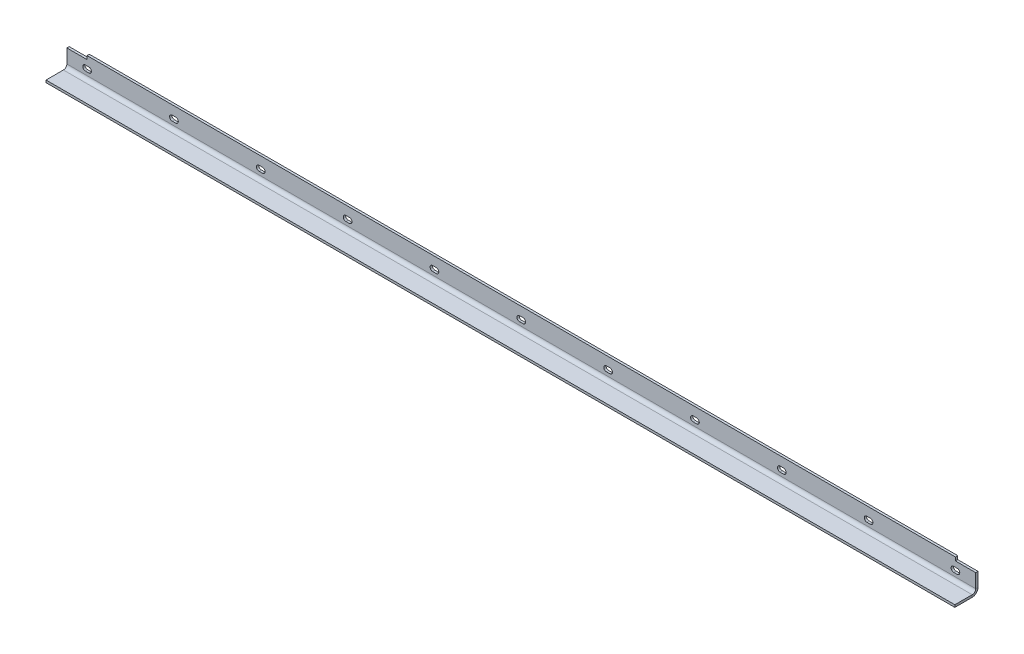
SolidWorks part; units mm, degrees
note: The reader was unsure of these and kept them because the rebuilt part matched: flange length of "Edge-Flange1".
material "ASTM A36 Steel"
ref_plane "Front Plane" through (0, 0, 0) normal (0, 0, 1) x (1, 0, 0)
ref_plane "Top Plane" through (0, 0, 0) normal (0, 1, 0) x (1, 0, 0)
ref_plane "Right Plane" through (0, 0, 0) normal (1, 0, 0) x (0, 0, -1)
sketch "Sketch1" plane through (0, 0, 0) normal (0, 1, 0) x (1, 0, 0)
  line L1 (305.3763, 40) -> (-1264.6237, 40)
  line L2 (305.3763, 40) -> (305.3763, 0)
  line L3 (305.3763, 0) -> (-1264.6237, 0)
  line L4 (-1264.6237, 40) -> (-1264.6237, 0)
  dimension "D1" = 40
  dimension "D2" = 1570
base flange "Base-Flange1" sketch "Sketch1" thickness 4 reverse thickness direction no parameters "D1"=2.5
edge flange "Edge-Flange1" sketch "Sketch8" flange angle 90 flange length 40 flange position material inside bend radius 6 thickness 4 relief rectangular parameters "D6"=10
sketch "Sketch8" plane through (0, 0, -40) normal (0, 0, 1) x (1, 0, 0)
  line L1 (305.3763, 0) -> (-1264.6237, 0) construction
  line L2 (-1264.6237, 0) -> (-1264.6237, 36)
  line L3 (-1264.6237, 36) -> (305.3763, 36)
  line L4 (305.3763, 36) -> (305.3763, 0)
  line L5 (305.3763, 0) -> (-1264.6237, 0)
bend "EdgeBend1" bend radius 6 bend angle 90 parameters "D5"=1
sketch "Sketch9" plane through (0, 0, -36) normal (0, 0, 1) x (1, 0, 0)
  line L0 (305.3763, 36) -> (305.3763, 30)
  line L1 (305.3763, 6) -> (305.3763, 36) construction
  line L2 (305.3763, 30) -> (270.3763, 30)
  line L3 (270.3763, 30) -> (270.3763, 36)
  line L4 (305.3763, 36) -> (-1264.6237, 36) construction
  line L5 (270.3763, 36) -> (305.3763, 36)
  line L6 (-1264.6237, 36) -> (-1264.6237, 30)
  line L7 (-1264.6237, 36) -> (-1264.6237, 6) construction
  line L8 (-1264.6237, 30) -> (-1229.6237, 30)
  line L9 (-1229.6237, 30) -> (-1229.6237, 36)
  line L10 (-1229.6237, 36) -> (-1264.6237, 36)
  dimension "D1" = 35
  dimension "D2" = 6
  dimension "D3" = 35
extrude "Cut-Extrude1" cut sketch "Sketch9" against normal blind 10 normal cut yes
sketch "Sketch10" plane through (0, 0, -36) normal (0, 0, 1) x (1, 0, 0)
  line L0 (273.3763, 16) -> (267.3763, 16) construction
  line L1 (273.3763, 11.5) -> (267.3763, 11.5)
  line L2 (273.3763, 20.5) -> (267.3763, 20.5)
  line L3 (305.3763, 6) -> (305.3763, 30) construction
  line L4 (270.3763, 36) -> (-1229.6237, 36) construction
  arc A0 (273.3763, 11.5) -> (273.3763, 20.5) centre (273.3763, 16) ccw
  arc A1 (267.3763, 20.5) -> (267.3763, 11.5) centre (267.3763, 16) ccw
  point P2 (270.3763, 16)
  dimension "D1" = 32
  dimension "D2" = 9
  dimension "D3" = 20
  dimension "D4" = 6
extrude "Cut-Extrude2" cut sketch "Sketch10" against normal blind 10 normal cut yes
pattern_linear "LPattern1" count 11 spacing 150 along (-1, 0, 0) of "Cut-Extrude2"
sketch "Bend-Lines1" [suppressed] plane through (0, 0, 0) normal (0, 1, 0) x (1, 0, 0)
sketch "Bounding-Box1" [suppressed] plane through (0, 0, 0) normal (0, 1, 0) x (1, 0, 0)
sheet metal parameters "Sheet-Metal1" thickness 4 parameters "D1"=2.5
flat pattern "Flat-Pattern1" [suppressed]
sketch "Bend-Lines2" plane through (0, 0, 0) normal (0, 1, 0) x (1, 0, 0)
sketch3d "Bounding-Box2" [suppressed]
  line L0 (-305.3763, 40, 0) -> (1264.6237, 40, 0) construction
  line L1 (-305.3763, 0, 0) -> (1264.6237, 0, 0) construction
  line L2 (-305.3763, 40, 0) -> (-305.3763, 0, 0) construction
  line L3 (1264.6237, 40, 0) -> (1264.6237, 0, 0) construction
sheet metal parameters "Sheet-Metal2" thickness 4 parameters "D1"=2.5
flat pattern "Flat-Pattern1"
sketch "Bend-Lines2" plane through (0, 0, 0) normal (0, 1, 0) x (1, 0, 0)
  line L0 (305.3763, 36.2832) -> (-1264.6237, 36.2832) construction
  line L1 (305.3763, 36.2832) -> (-1264.6237, 36.2832) construction
sketch3d "Bounding-Box2" [suppressed]
  line L0 (305.3763, 72.5664, 0) -> (-1264.6237, 72.5664, 0) construction
  line L1 (305.3763, 0, 0) -> (-1264.6237, 0, 0) construction
  line L2 (305.3763, 72.5664, 0) -> (305.3763, 0, 0) construction
  line L3 (-1264.6237, 72.5664, 0) -> (-1264.6237, 0, 0) construction
bend of the flat pattern "Flatten-<EdgeBend1>1"
sheet metal parameters "Sheet-Metal3" thickness 4 parameters "D1"=2.5
flat pattern "Flat-Pattern1"
sketch "Bend-Lines2" plane through (0, 0, 0) normal (0, 1, 0) x (1, 0, 0)
  line L0 (305.3763, 36.2832) -> (-1264.6237, 36.2832) construction
  line L1 (305.3763, 36.2832) -> (-1264.6237, 36.2832) construction
sketch3d "Bounding-Box2" [suppressed]
  line L0 (305.3763, 72.5664, 0) -> (-1264.6237, 72.5664, 0) construction
  line L1 (305.3763, 0, 0) -> (-1264.6237, 0, 0) construction
  line L2 (305.3763, 72.5664, 0) -> (305.3763, 0, 0) construction
  line L3 (-1264.6237, 72.5664, 0) -> (-1264.6237, 0, 0) construction
bend of the flat pattern "Flatten-<EdgeBend1>1"
sheet metal parameters "Sheet-Metal4" thickness 4 parameters "D1"=2.5
flat pattern "Flat-Pattern1"
sketch "Bend-Lines2" plane through (0, 0, 0) normal (0, 1, 0) x (1, 0, 0)
  line L0 (305.3763, 36.2832) -> (-1264.6237, 36.2832) construction
  line L1 (305.3763, 36.2832) -> (-1264.6237, 36.2832) construction
sketch3d "Bounding-Box2" [suppressed]
  line L0 (305.3763, 72.5664, 0) -> (-1264.6237, 72.5664, 0) construction
  line L1 (305.3763, 0, 0) -> (-1264.6237, 0, 0) construction
  line L2 (305.3763, 72.5664, 0) -> (305.3763, 0, 0) construction
  line L3 (-1264.6237, 72.5664, 0) -> (-1264.6237, 0, 0) construction
bend of the flat pattern "Flatten-<EdgeBend1>1"
sheet metal parameters "Sheet-Metal5" thickness 4 parameters "D1"=2.5
flat pattern "Flat-Pattern1"
sketch "Bend-Lines2" plane through (0, 0, 0) normal (0, 1, 0) x (1, 0, 0)
  line L0 (305.3763, 36.2832) -> (-1264.6237, 36.2832) construction
  line L1 (305.3763, 36.2832) -> (-1264.6237, 36.2832) construction
sketch3d "Bounding-Box2" [suppressed]
  line L0 (305.3763, 72.5664, 0) -> (-1264.6237, 72.5664, 0) construction
  line L1 (305.3763, 0, 0) -> (-1264.6237, 0, 0) construction
  line L2 (305.3763, 72.5664, 0) -> (305.3763, 0, 0) construction
  line L3 (-1264.6237, 72.5664, 0) -> (-1264.6237, 0, 0) construction
bend of the flat pattern "Flatten-<EdgeBend1>1"
